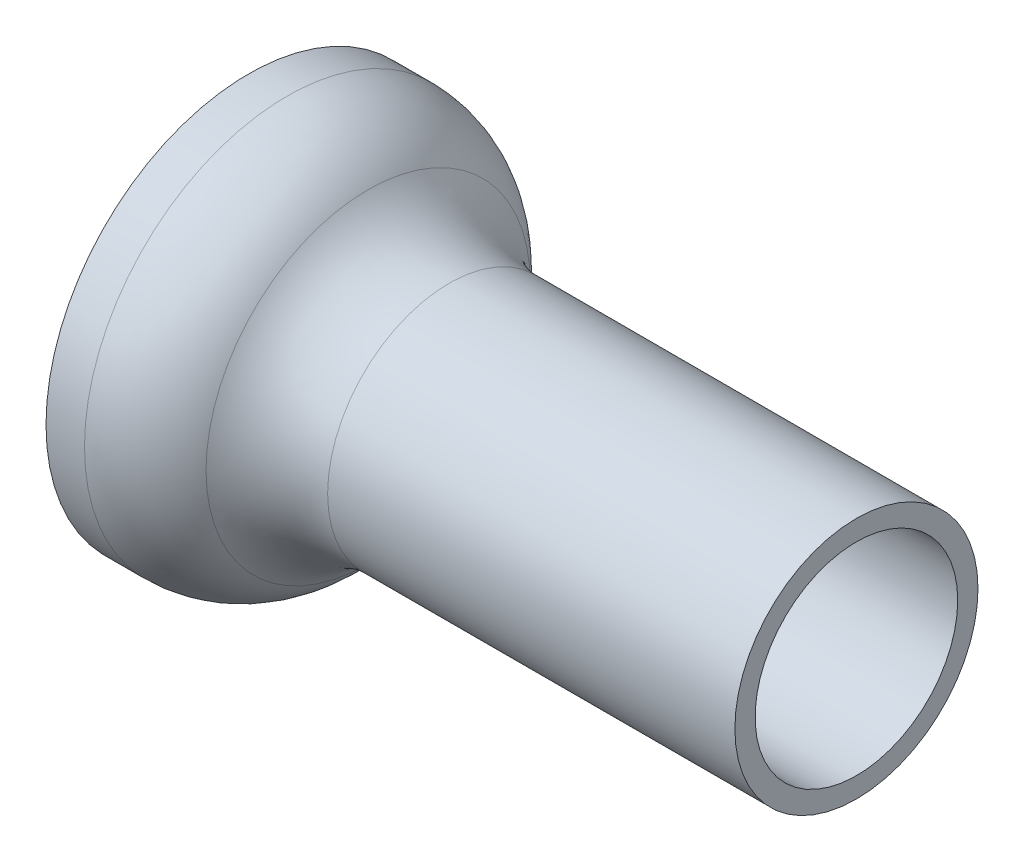
SolidWorks part; units mm, degrees
ref_plane "Front Plane" through (0, 0, 0) normal (0, 0, 1) x (1, 0, 0)
ref_plane "Top Plane" through (0, 0, 0) normal (0, 1, 0) x (1, 0, 0)
ref_plane "Right Plane" through (0, 0, 0) normal (1, 0, 0) x (0, 0, -1)
sketch "Sketch1" plane through (0, 0, 0) normal (1, 0, 0) x (0, 0, -1)
  circle A0 centre (0, 0) radius 2.5
  circle A1 centre (0, 0) radius 3
  dimension "D1" = 5
  dimension "D2" = 6
extrude "Boss-Extrude1" add sketch "Sketch1" along normal blind 15
sketch "Sketch2" plane through (0, 0, 0) normal (1, 0, 0) x (0, 0, -1)
  circle A0 centre (0, 0) radius 5
  circle A1 centre (0, 0) radius 3 construction
  circle A2 centre (0, 0) radius 3
  dimension "D1" = 10
extrude "Boss-Extrude2" add sketch "Sketch2" along normal blind 2.5
fillet "Fillet1" radius 2.5 1 edges at (2.5, 0, -3)
fillet "Fillet2" radius 2.5 1 edges at (2.5, 0, -5)
